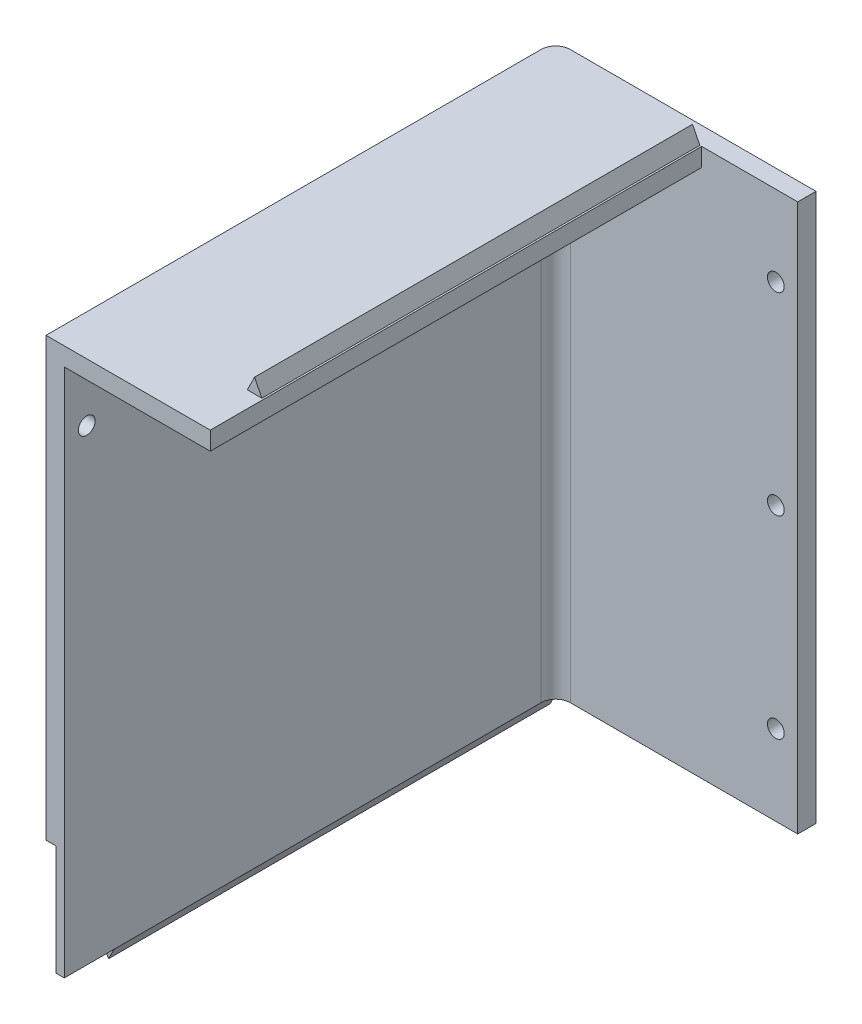
SolidWorks part; units mm, degrees
material "PLA"
ref_plane "Front Plane" through (0, 0, 0) normal (0, 0, 1) x (1, 0, 0)
ref_plane "Top Plane" through (0, 0, 0) normal (0, 1, 0) x (1, 0, 0)
ref_plane "Right Plane" through (0, 0, 0) normal (1, 0, 0) x (0, 0, -1)
sketch "Sketch1" plane through (0, 0, 0) normal (0, 1, 0) x (1, 0, 0)
  line L0 (-20.2729, -55.3943) -> (-17.8261, -54.8814)
  line L1 (-21.0173, 14.4257) -> (-5.3573, 14.4257)
  line L3 (-18.5173, 11.9257) -> (-5.3573, 11.9257)
  line L4 (-5.3573, 14.4257) -> (-5.3573, 11.9257)
  line L6 (-21.0173, 14.4257) -> (-21.0173, -48.2143)
  line L8 (-18.5173, 11.9257) -> (-18.5173, -48.2143)
  arc A0 (-21.0173, -48.2143) -> (-20.2729, -55.3943) centre (13.9827, -48.2143) ccw
  arc A1 (-18.5173, -48.2143) -> (-17.8261, -54.8814) centre (13.9827, -48.2143) ccw
  dimension "D1" = 2.5
  dimension "D2" = 15.66
  dimension "D3" = 2.5
  dimension "D4" = 62.64
  dimension "D5" = 32.5
  dimension "D6" = 7.18
extrude "Boss-Extrude1" add sketch "Sketch1" along normal blind 75
fillet "Fillet1" radius 2 2 edges at (-21.0173, 37.5, -14.4257) (-18.5173, 37.5, -11.9257)
sketch "Sketch2" plane through (0, 0, -11.9257) normal (0, 0, 1) x (1, 0, 0)
  circle A0 centre (-7.5209, 63.9221) radius 1.0847
  circle A1 centre (-7.4883, 37.5) radius 1
  circle A2 centre (-7.4883, 12.5) radius 1
sketch "Sketch3" plane through (-16.0173, 0, 0) normal (-1, 0, 0) x (0, 0, 1)
  circle A0 centre (51.2187, 64) radius 1
  circle A1 centre (52.4166, 13.8054) radius 1
sketch "Sketch4" plane through (-18.5173, 0, 0) normal (1, 0, 0) x (0, 0, -1)
  line L0 (-48.2143, 0) -> (9.9257, 0) construction
  line L1 (-38.2865, 0) -> (-64.1165, 0)
  line L2 (-38.2865, 0) -> (-38.2865, 76.9648)
  line L3 (-38.2865, 76.9648) -> (-64.1165, 76.9648)
  line L4 (-64.1165, 0) -> (-64.1165, 76.9648)
extrude "Cut-Extrude3" cut sketch "Sketch4" along normal blind 10
ref_plane "Plane1" through (0, 0, 48.2143) normal (0, 0, 1) x (0, -1, 0)
sketch "Sketch7" plane through (0, 0, 48.2143) normal (0, 0, 1) x (0, -1, 0)
  line L1 (-75, -21.0173) -> (0, -21.0173)
  line L2 (-75, -21.0173) -> (-75, -18.5173)
  line L3 (-75, -18.5173) -> (0, -18.5173)
  line L4 (0, -21.0173) -> (0, -18.5173)
  point P5 (-75, -18.5173)
  dimension "D1" = 0
extrude "Boss-Extrude2" add sketch "Sketch7" along normal up to vertex (7.18 mm away) up to point (-20.273, 75, 55.3943)
ref_plane "Plane2" through (-18.5173, 75, -9.9257) normal (0, 0, -1) x (-1, 0, 0)
sketch "Sketch9" plane through (-5.3573, 0, 0) normal (1, 0, 0) x (0, 0, -1)
  line L1 (11.9257, 75) -> (14.4257, 75)
  line L2 (11.9257, 75) -> (11.9257, 0)
  line L3 (11.9257, 0) -> (14.4257, 0)
  line L4 (14.4257, 75) -> (14.4257, 0)
extrude "Boss-Extrude3" add sketch "Sketch9" along normal blind 20
sketch "Sketch10" plane through (-18.5173, 0, 0) normal (1, 0, 0) x (0, 0, -1)
  line L1 (-55.3943, 75) -> (13.1057, 75)
  line L2 (-55.3943, 75) -> (-55.3943, 72.5)
  line L3 (-55.3943, 72.5) -> (13.1057, 72.5)
  line L4 (13.1057, 75) -> (13.1057, 72.5)
  dimension "D1" = 68.5
  dimension "D2" = 2.5
extrude "Boss-Extrude4" add sketch "Sketch10" along normal blind 20
sketch "Sketch11" plane through (0, 0, 55.3943) normal (0, 0, 1) x (1, 0, 0)
  line L0 (-20.7673, 0) -> (-18.7673, 0)
  line L1 (-21.0173, 0) -> (-18.5173, 0) construction
  line L2 (-20.7673, 0) -> (-19.7673, -2)
  line L3 (-19.7673, -2) -> (-18.7673, 0)
  point P4 (-19.7673, 0)
  dimension "D1" = 0.25
  dimension "D2" = 2
  dimension "D3" = 0
  dimension "D4" = 2
extrude "Boss-Extrude5" add sketch "Sketch11" against normal up to vertex (67.82 mm away) up to point (-21.0173, 0, -12.4257)
sketch "Sketch12" plane through (0, 0, 55.3943) normal (0, 0, 1) x (1, 0, 0)
  line L0 (-20.7673, 0) -> (-18.7673, 0)
  line L1 (-18.7673, 0) -> (-19.7673, -2)
  line L2 (-19.7673, -2) -> (-20.7673, 0)
extrude "Cut-Extrude4" cut sketch "Sketch12" against normal blind 7.32
sketch "Sketch13" plane through (0, 0, 55.3943) normal (0, 0, 1) x (1, 0, 0)
  line L1 (-21.0173, 0) -> (-19.6673, 0)
  line L2 (-21.0173, 0) -> (-21.0173, 15.1)
  line L3 (-21.0173, 15.1) -> (-19.6673, 15.1)
  line L4 (-19.6673, 0) -> (-19.6673, 15.1)
  dimension "D1" = 1.35
  dimension "D2" = 15.1
extrude "Cut-Extrude5" cut sketch "Sketch13" against normal blind 7.32
ref_plane "Plane3" through (0, 0, 48.0743) normal (0, 0, 1) x (1, 0, 0)
sketch "Sketch14" plane through (0, 0, 48.0743) normal (0, 0, 1) x (1, 0, 0)
  line L0 (-21.0173, 75) -> (-21.0173, 15.1) construction
  line L1 (-21.0173, 75) -> (-21.0173, 15.1)
  line L3 (1.4827, 75) -> (-21.0173, 75) construction
  line L6 (1.2327, 75) -> (-0.7673, 75)
  line L7 (-0.7673, 75) -> (0.2327, 77)
  line L8 (0.2327, 77) -> (1.2327, 75)
  point P6 (-19.7673, 75)
  point P7 (-19.7673, 77)
  point P11 (0.2327, 75)
  point P12 (0.2327, 77)
  dimension "D4" = 2
  dimension "D5" = 0.25
  dimension "D6" = 2
sketch "Sketch15" plane through (0, 0, -14.4257) normal (0, 0, -1) x (-1, 0, 0)
  circle A0 centre (-11.6427, 64) radius 1.15
  circle A1 centre (-11.6427, 37.5) radius 1.15
  circle A2 centre (-11.6427, 11) radius 1.15
  dimension "D1" = 2.3
  dimension "D2" = 3
  dimension "D3" = 11
  dimension "D4" = 3
extrude "Cut-Extrude6" cut sketch "Sketch15" against normal blind 7.32
sketch "Sketch16" plane through (-21.0173, 0, 0) normal (-1, 0, 0) x (0, 0, 1)
  line L0 (55.3943, 75) -> (55.3943, 15.1) construction
  line L1 (-12.4257, 75) -> (55.3943, 75) construction
  circle A0 centre (52.3143, 64) radius 1.15
  dimension "D1" = 2.3
  dimension "D2" = 3.08
  dimension "D3" = 11
extrude "Cut-Extrude7" cut sketch "Sketch16" against normal blind 7.32
extrude "Boss-Extrude8" add sketch "Sketch14" against normal up to vertex (60 mm away) contours L6 L7 L8 up to point (1.4827, 75, -11.9257)
chamfer "Chamfer1" distance 0.75 angle 45 1 edges at (-21.0173, 64, 53.4643)
chamfer "Chamfer2" distance 0.75 angle 45 3 edges at (10.4927, 11, -14.4257) (10.4927, 37.5, -14.4257) (10.4927, 64, -14.4257)
